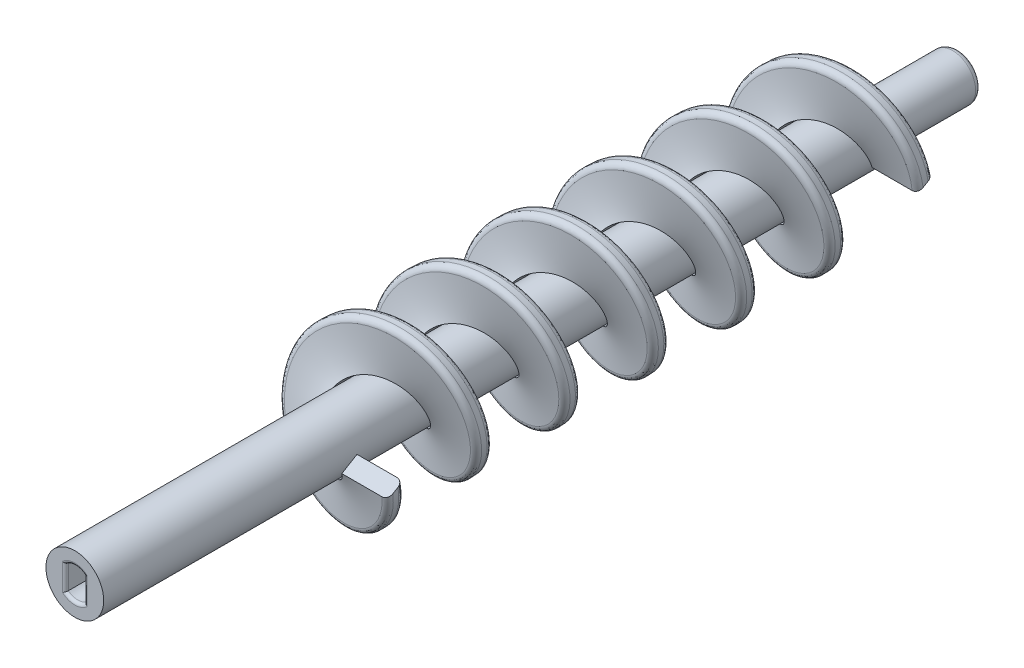
SolidWorks part; units mm, degrees
ref_plane "Front Plane" through (0, 0, 0) normal (0, 0, 1) x (1, 0, 0)
ref_plane "Top Plane" through (0, 0, 0) normal (0, 1, 0) x (1, 0, 0)
ref_plane "Right Plane" through (0, 0, 0) normal (1, 0, 0) x (0, 0, -1)
sketch "Sketch2" plane through (0, 0, 0) normal (0, 0, 1) x (1, 0, 0)
  circle A0 centre (0, 0) radius 4.9
  dimension "D1" = 9.8
extrude "Boss-Extrude1" add sketch "Sketch2" along normal mid plane 133
sketch "Sketch3" plane through (0, 0, -66.5) normal (0, 0, -1) x (-1, 0, 0)
  circle A0 centre (0, 0) radius 4
curve "Helix/Spiral1" pitch 15 height 90 radius 4 centre (0, 0, -66.5) axis (0, 0, 1) start towards (1, 0, 0)
ref_plane "Plane1" through (4, 0, -66.5) normal (0, 0.8587, 0.5125) x (1, 0, 0)
sketch "Sketch5" plane through (4, 0, -66.5) normal (0, 0.8587, 0.5125) x (1, 0, 0)
  line L1 (0.9, 0) -> (7.7, 0)
  line L2 (0.9, 0) -> (0.9, -3)
  line L3 (0.9, -3) -> (7.7, -3)
  line L4 (8.7, -1) -> (8.7, -2)
  arc A0 (7.7, -3) -> (8.7, -2) centre (7.7, -2) ccw
  arc A1 (7.7, 0) -> (8.7, -1) centre (7.7, -1) cw
  ellipse E0 centre (-4, 0) end of major axis (-8.9, 0) minor radius 2.5112 construction
  point P14 (8.7, 0)
  dimension "D3" = 1
  dimension "D1" = 7.8
  dimension "D2" = 3
sweep "Sweep1" add profiles "Sketch5" path "Helix/Spiral1"
sketch "Sketch6" plane through (0, 0, 66.5) normal (0, 0, 1) x (1, 0, 0)
  line L1 (-1.6, -2.0494) -> (1.6, -2.0494)
  line L2 (-1.6, -2.0494) -> (-1.6, 2.0494)
  line L3 (-1.6, 2.0494) -> (1.6, 2.0494)
  line L4 (1.6, -2.0494) -> (1.6, 2.0494)
  line L5 (-1.6, -2.0494) -> (1.6, 2.0494) construction
  line L6 (-1.6, 2.0494) -> (1.6, -2.0494) construction
  circle A0 centre (0, 0) radius 2.6
  dimension "D1" = 5.2
  dimension "D2" = 3.2
extrude "Cut-Extrude1" cut sketch "Sketch6" against normal blind 9 contours L3 A0 | L1 L4 L3 L2 | L1 A0 region at (0, 0, 66.5) region at (0, -2.2718, 66.5) region at (0, 2.2718, 66.5)
sketch "Sketch7" plane through (0, 0, -66.5) normal (0, 0, -1) x (-1, 0, 0)
  circle A0 centre (0, 0) radius 3.9
  dimension "D1" = 7.8
extrude "Boss-Extrude3" add sketch "Sketch7" along normal blind 17
fillet "Fillet1" radius 1 1 edges at (-3.9, 0, -83.5)
fillet "Fillet2" radius 0.5 4 edges at (0, -2.6, 66.5) (1.6, 0, 66.5) (0, 2.6, 66.5) (-1.6, 0, 66.5)
